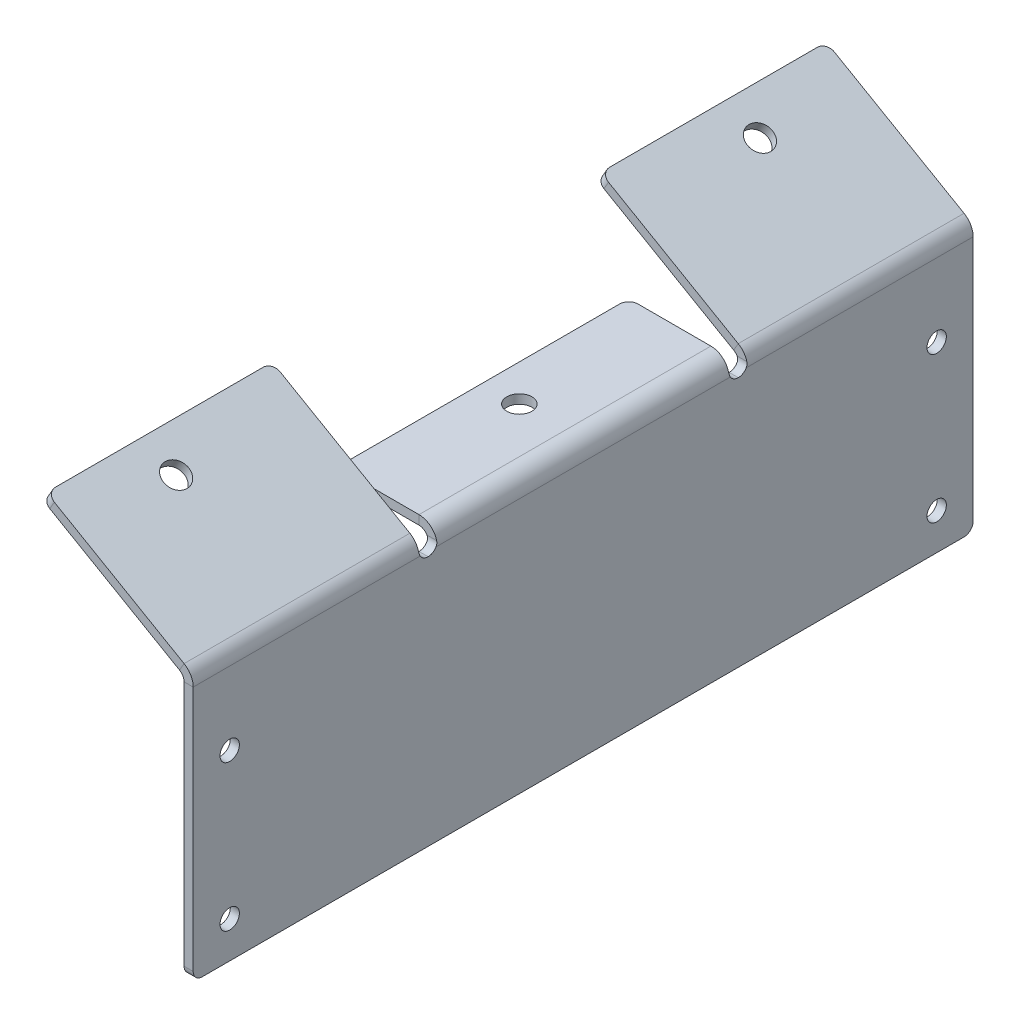
SolidWorks part; units mm, degrees
note: The reader was unsure of these and kept them because the rebuilt part matched: flange length of "Edge-Flange1", "Edge-Flange2".
material "5052-H32"
ref_plane "Front Plane" through (0, 0, 0) normal (0, 0, 1) x (1, 0, 0)
ref_plane "Top Plane" through (0, 0, 0) normal (0, 1, 0) x (1, 0, 0)
ref_plane "Right Plane" through (0, 0, 0) normal (1, 0, 0) x (0, 0, -1)
sketch "Sketch1" plane through (0, 0, 0) normal (1, 0, 0) x (0, 0, -1)
  line L0 (84.9338, 88.9) -> (186.5338, 88.9)
  line L1 (0, 0) -> (271.4676, 0)
  line L2 (0, 0) -> (0, 88.9)
  line L4 (271.4676, 0) -> (271.4676, 88.9)
  line L7 (0, 88.9) -> (78.5838, 88.9)
  line L15 (78.5838, 88.9) -> (78.5838, 87.3125)
  line L16 (78.5838, 87.3125) -> (84.9338, 87.3125)
  line L17 (84.9338, 87.3125) -> (84.9338, 88.9)
  line L18 (186.5338, 88.9) -> (186.5338, 87.3125)
  line L19 (186.5338, 87.3125) -> (192.8838, 87.3125)
  line L20 (192.8838, 87.3125) -> (192.8838, 88.9)
  line L21 (192.8838, 88.9) -> (271.4676, 88.9)
  dimension "D1" = 271.4676
  dimension "D2" = 101.6
  dimension "D3" = 88.9
  dimension "D4" = 1.5875
  dimension "D5" = 1.5875
  dimension "D6" = 6.35
  dimension "D7" = 6.35
  dimension "D8" = 1.5875
base flange "Base-Flange1" sketch "Sketch1" thickness 3.175 reverse thickness direction no parameters "D1"=3.175
edge flange "Edge-Flange1" sketch "Sketch22" flange angle 90 flange length 31.75 flange position bend outside bend radius 3.175 thickness 3.175 relief rectangular parameters "D6"=10, "D8"=1
bend "EdgeBend3" bend radius 3.175 bend angle 90 parameters "D5"=1
sketch "Sketch22" plane through (-3.175, 88.9, 0) normal (0, 1, 0) x (0, 0, -1)
  line L0 (186.5338, 0) -> (84.9338, 0) construction
  line L1 (186.5338, 0) -> (84.9338, 0)
  line L2 (84.9338, 0) -> (84.9338, 31.75)
  line L3 (84.9338, 31.75) -> (186.5338, 31.75)
  line L4 (186.5338, 31.75) -> (186.5338, 0)
sketch "Sketch15" plane through (0, 95.25, 0) normal (0, 1, 0) x (1, 0, 0)
  line L11 (-34.925, 186.5338) -> (-34.925, 84.9338) construction
  circle A2 centre (-22.225, 135.7338) radius 4.3688
  dimension "D5" = 8.7376
  dimension "D1" = 135.7338
  dimension "D2" = 12.7
extrude "Cut-Extrude1" cut sketch "Sketch15" against normal through all normal cut yes
sketch "Sketch16" plane through (0, 0, 0) normal (1, 0, 0) x (0, 0, -1)
  line L1 (78.5838, 88.9) -> (0, 88.9) construction
  line L3 (135.7338, 88.9) -> (135.7338, 0) construction
  line L5 (0, 0) -> (271.4676, 0) construction
  line L6 (0, 88.9) -> (0, 0) construction
  line L9 (186.5338, 88.9) -> (84.9338, 88.9) construction
  circle A2 centre (12.7, 63.5) radius 3.3734
  circle A3 centre (12.7, 12.7) radius 3.3734
  circle A9 centre (258.7676, 12.7) radius 3.3734
  circle A10 centre (258.7676, 63.5) radius 3.3734
  dimension "D6" = 6.7469
  dimension "D2" = 12.7
  dimension "D5" = 25.4
  dimension "D7" = 50.8
extrude "Cut-Extrude2" cut sketch "Sketch16" against normal blind 3.175 normal cut yes
edge flange "Edge-Flange2" sketch "Sketch27" flange profiles "Sketch27", "Sketch30" flange angle 120 flange length 57.15 flange position bend outside bend radius 3.175 thickness 3.175 relief rectangular parameters "D6"=10, "D8"=1
sketch "Sketch27" plane through (-3.175, 88.9, 0) normal (0.5, 0.866, 0) x (0, 0, -1)
  line L2 (0, 0) -> (0, 57.15)
  line L3 (0, 57.15) -> (78.5838, 57.15)
  line L4 (78.5838, 57.15) -> (78.5838, 0)
  line L7 (78.5838, 0) -> (0, 0) construction
  line L8 (78.5838, 0) -> (0, 0)
sketch "Sketch30" plane through (-3.175, 88.9, 0) normal (0.5, 0.866, 0) x (0, 0, -1)
  line L0 (271.4676, 0) -> (192.8838, 0) construction
  line L1 (271.4676, 0) -> (192.8838, 0)
  line L2 (192.8838, 0) -> (192.8838, 57.15)
  line L3 (192.8838, 57.15) -> (271.4676, 57.15)
  line L4 (271.4676, 57.15) -> (271.4676, 0)
bend "EdgeBend4" bend radius 3.175 bend angle 60 parameters "D5"=2
bend "EdgeBend6" bend radius 3.175 bend angle 60 parameters "D5"=4
sketch "Sketch31" plane through (40.0823, 69.4246, 0) normal (0.5, 0.866, 0) x (0.866, -0.5, 0)
  line L0 (-105.2662, 271.4676) -> (-105.2662, 192.8838) construction
  line L2 (-105.2662, 0) -> (-49.9493, 0) construction
  circle A0 centre (-92.5662, 237.3338) radius 4.3688
  circle A1 centre (-92.5662, 34.1338) radius 4.3688
  dimension "D2" = 8.7376
  dimension "D1" = 12.7
  dimension "D3" = 203.2
  dimension "D4" = 34.1338
extrude "Cut-Extrude3" cut sketch "Sketch31" against normal blind 3.175 normal cut yes
fillet "Fillet3" radius 3.175 12 edges at (-51.8746, 120.6829, -78.5838) (-1.5875, 87.3125, -78.5838) (-1.5875, 87.3125, -84.9338) (-34.925, 93.6625, -84.9338) (-34.925, 93.6625, -186.5338) (-1.5875, 87.3125, -186.5338) (-1.5875, 87.3125, -192.8838) (-51.8746, 120.6829, -192.8838) (-51.8746, 120.6829, -271.4676) (-1.5875, 0, -271.4676) (-1.5875, 0, 0) (-51.8746, 120.6829, 0)
sketch "Bend-Lines1" [suppressed] plane through (0, 0, 0) normal (0, 1, 0) x (1, 0, 0)
sketch "Bounding-Box1" [suppressed] plane through (0, 0, 0) normal (0, 1, 0) x (1, 0, 0)
sheet metal parameters "Sheet-Metal1" thickness 3.175 parameters "D1"=3.175
flat pattern "Flat-Pattern1" [suppressed]
sketch "Bend-Lines2" plane through (0, 0, 0) normal (0, 1, 0) x (1, 0, 0)
sketch3d "Bounding-Box2" [suppressed]
  line L0 (271.4676, 0, 0) -> (0, 0, 0) construction
  line L1 (271.4676, 92.075, 0) -> (0, 92.075, 0) construction
  line L2 (271.4676, 0, 0) -> (271.4676, 92.075, 0) construction
  line L3 (0, 0, 0) -> (0, 92.075, 0) construction
sheet metal parameters "Sheet-Metal2" thickness 3.175 parameters "D1"=3.175
flat pattern "Flat-Pattern1"
sketch "Bend-Lines2" plane through (0, 0, 0) normal (1, 0, 0) x (0, 0, -1)
  line L0 (186.5338, 95.8155) -> (84.9338, 95.8155) construction
  line L1 (186.5338, 95.8155) -> (84.9338, 95.8155) construction
sketch3d "Bounding-Box2" [suppressed]
  line L0 (271.4676, 0, 0) -> (0, 0, 0) construction
  line L1 (271.4676, 128.1309, 0) -> (0, 128.1309, 0) construction
  line L2 (271.4676, 0, 0) -> (271.4676, 128.1309, 0) construction
  line L3 (0, 0, 0) -> (0, 128.1309, 0) construction
bend of the flat pattern "Flatten-<EdgeBend3>1"
sheet metal parameters "Sheet-Metal3" thickness 3.175 parameters "D1"=3.175
flat pattern "Flat-Pattern1"
sketch "Bend-Lines2" plane through (0, 0, 0) normal (1, 0, 0) x (0, 0, -1)
  line L6 (186.5338, 95.8155) -> (84.9338, 95.8155) construction
  line L7 (186.5338, 95.8155) -> (84.9338, 95.8155) construction
  point P0 (523.3416, 67.2405)
  point P1 (388.6708, 67.2405)
  point P2 (337.8708, 67.2405)
  point P3 (185.4708, 67.2405)
  point P4 (134.6708, 67.2405)
  point P5 (0, 67.2405)
sketch3d "Bounding-Box2" [suppressed]
  line L0 (271.4676, 0, 0) -> (0, 0, 0) construction
  line L1 (271.4676, 128.1309, 0) -> (0, 128.1309, 0) construction
  line L2 (271.4676, 0, 0) -> (271.4676, 128.1309, 0) construction
  line L3 (0, 0, 0) -> (0, 128.1309, 0) construction
bend of the flat pattern "Flatten-<EdgeBend3>2"
sheet metal parameters "Sheet-Metal4" thickness 3.175 parameters "D1"=3.175
flat pattern "Flat-Pattern1"
sketch "Bend-Lines2" plane through (0, 0, 0) normal (1, 0, 0) x (0, 0, -1)
  line L6 (186.5338, 92.6405) -> (84.9338, 92.6405) construction
  line L7 (186.5338, 92.6405) -> (84.9338, 92.6405) construction
sketch3d "Bounding-Box2" [suppressed]
  line L0 (271.4676, 0, 0) -> (0, 0, 0) construction
  line L1 (271.4676, 124.9559, 0) -> (0, 124.9559, 0) construction
  line L2 (271.4676, 0, 0) -> (271.4676, 124.9559, 0) construction
  line L3 (0, 0, 0) -> (0, 124.9559, 0) construction
bend of the flat pattern "Flatten-<EdgeBend3>3"
sheet metal parameters "Sheet-Metal5" thickness 3.175 parameters "D1"=3.175
flat pattern "Flat-Pattern1"
sketch "Bend-Lines2" plane through (0, 0, 0) normal (1, 0, 0) x (0, 0, -1)
  line L1 (78.5838, 92.017) -> (0, 92.017) construction
  line L3 (78.5838, 92.017) -> (0, 92.017) construction
  line L4 (271.4676, 92.017) -> (192.8838, 92.017) construction
  line L5 (271.4676, 92.017) -> (192.8838, 92.017) construction
  line L6 (186.5338, 92.6405) -> (84.9338, 92.6405) construction
  line L7 (186.5338, 92.6405) -> (84.9338, 92.6405) construction
sketch3d "Bounding-Box2" [suppressed]
  line L0 (271.4676, 0, 0) -> (0, 0, 0) construction
  line L1 (271.4676, 130.7978, 0) -> (0, 130.7978, 0) construction
  line L2 (271.4676, 0, 0) -> (271.4676, 130.7978, 0) construction
  line L3 (0, 0, 0) -> (0, 130.7978, 0) construction
bend of the flat pattern "Flatten-<EdgeBend3>3"
bend of the flat pattern "Flatten-<EdgeBend4>1"
bend of the flat pattern "Flatten-<EdgeBend6>1"
sheet metal parameters "Sheet-Metal6" thickness 3.175 parameters "D1"=3.175
flat pattern "Flat-Pattern1"
sketch "Bend-Lines2" plane through (0, 0, 0) normal (1, 0, 0) x (0, 0, -1)
  line L1 (78.5838, 91.3936) -> (0, 91.3936) construction
  line L3 (78.5838, 91.3936) -> (0, 91.3936) construction
  line L4 (271.4676, 91.3936) -> (192.8838, 91.3936) construction
  line L5 (271.4676, 91.3936) -> (192.8838, 91.3936) construction
  line L6 (186.5338, 92.6405) -> (84.9338, 92.6405) construction
  line L7 (186.5338, 92.6405) -> (84.9338, 92.6405) construction
sketch3d "Bounding-Box2" [suppressed]
  line L0 (271.4676, 0, 0) -> (0, 0, 0) construction
  line L1 (271.4676, 149.2042, 0) -> (0, 149.2042, 0) construction
  line L2 (271.4676, 0, 0) -> (271.4676, 149.2042, 0) construction
  line L3 (0, 0, 0) -> (0, 149.2042, 0) construction
bend of the flat pattern "Flatten-<EdgeBend3>3"
bend of the flat pattern "Flatten-<EdgeBend4>1"
bend of the flat pattern "Flatten-<EdgeBend6>1"
